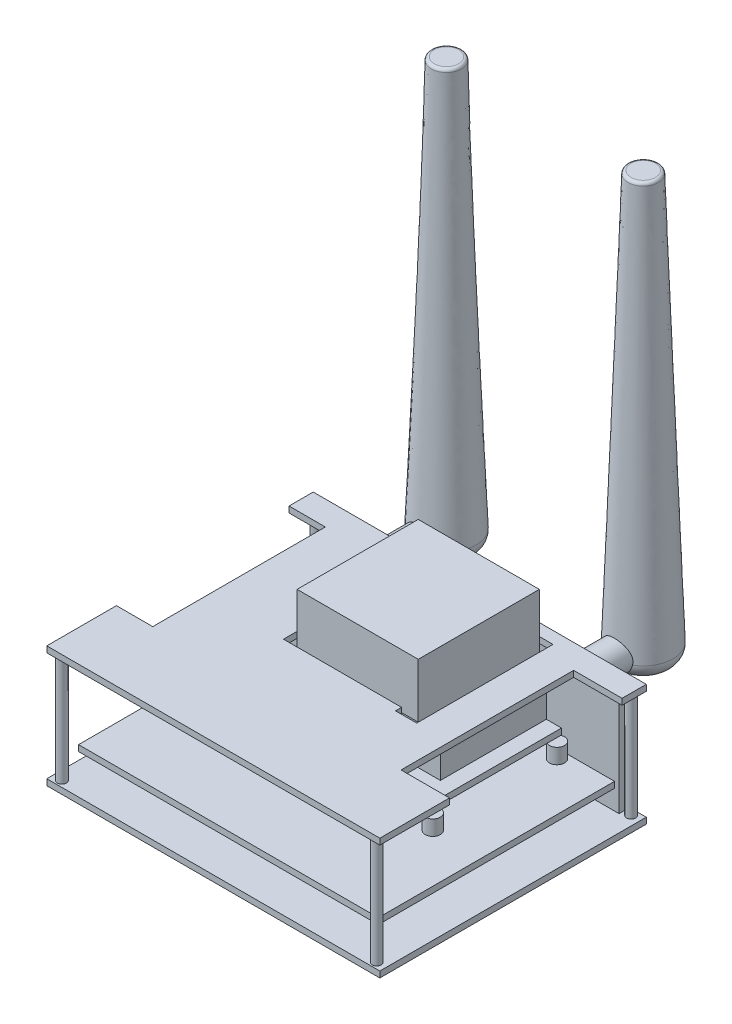
SolidWorks part; units mm, degrees
ref_plane "Front" through (0, 0, 0) normal (0, 0, 1) x (1, 0, 0)
ref_plane "Top" through (0, 0, 0) normal (0, 1, 0) x (1, 0, 0)
ref_plane "Right" through (0, 0, 0) normal (1, 0, 0) x (0, 0, -1)
sketch "草图1" plane through (0, 0, 0) normal (0, 1, 0) x (1, 0, 0)
  line L1 (0, 0) -> (110, 0)
  line L2 (0, 0) -> (0, 88)
  line L3 (0, 88) -> (110, 88)
  line L4 (110, 0) -> (110, 88)
  dimension "D1" = 110
  dimension "D2" = 88
extrude "凸台-拉伸1" add sketch "草图1" along normal blind 2
sketch "草图2" plane through (0, 2, 0) normal (0, 1, 0) x (1, 0, 0)
  line L0 (0, 88) -> (0, 0) construction
  line L1 (0, 0) -> (110, 0) construction
  line L2 (110, 88) -> (0, 88) construction
  line L3 (110, 0) -> (110, 88) construction
  circle A0 centre (3, 2) radius 1.5
  circle A1 centre (107, 86) radius 1.5
  circle A2 centre (3, 86) radius 1.5
  circle A3 centre (107, 2) radius 1.5
  dimension "D1" = 3
  dimension "D2" = 2
  dimension "D3" = 3
  dimension "D4" = 2
  dimension "D5" = 2
  dimension "D6" = 3
  dimension "D7" = 3
  dimension "D8" = 2
extrude "凸台-拉伸2" add sketch "草图2" along normal blind 36
sketch "草图3" plane through (0, 38, 0) normal (0, 1, 0) x (1, 0, 0)
  line L0 (110, 23) -> (110, 0)
  line L1 (0, 88) -> (110, 88)
  line L2 (0, 88) -> (0, 80)
  line L3 (0, 0) -> (110, 0)
  line L4 (110, 88) -> (110, 80)
  line L5 (110, 80) -> (94, 80)
  line L7 (110, 23) -> (94, 23)
  line L8 (94, 80) -> (94, 23)
  line L9 (0, 80) -> (12, 80)
  line L11 (0, 23) -> (12, 23)
  line L12 (12, 80) -> (12, 23)
  line L13 (37.1847, 84) -> (83.1847, 84)
  line L14 (37.1847, 84) -> (37.1847, 41)
  line L15 (37.1847, 41) -> (76.1847, 41)
  line L16 (83.1847, 84) -> (83.1847, 41)
  line L17 (0, 23) -> (0, 0)
  line L20 (83.1847, 41) -> (83.1847, 39)
  line L21 (83.1847, 39) -> (76.1847, 39)
  line L22 (76.1847, 41) -> (76.1847, 39)
  dimension "D1" = 16
  dimension "D2" = 57
  dimension "D3" = 23
  dimension "D4" = 12
  dimension "D5" = 57
  dimension "D6" = 8
  dimension "D7" = 39
  dimension "D8" = 7
  dimension "D9" = 43
  dimension "D10" = 4
  dimension "D11" = 2
extrude "凸台-拉伸3" add sketch "草图3" along normal blind 2
sketch "草图4" plane through (0, 2, 0) normal (0, 1, 0) x (1, 0, 0)
  line L0 (110, 88) -> (0, 88) construction
  line L1 (5.5, 86.5) -> (104.5, 86.5)
  line L2 (5.5, 86.5) -> (5.5, 84.5)
  line L3 (5.5, 84.5) -> (104.5, 84.5)
  line L4 (104.5, 86.5) -> (104.5, 84.5)
  circle A0 centre (3, 86) radius 1.5 construction
  circle A1 centre (107, 86) radius 1.5 construction
  point P6 (5.5, 85.5)
  dimension "D4" = 2.5
  dimension "D1" = 1.5
  dimension "D2" = 2
  dimension "D3" = 2.5
extrude "凸台-拉伸4" add sketch "草图4" along normal blind 36
sketch "草图5" plane through (0, 0, -86.5) normal (0, 0, -1) x (-1, 0, 0)
  line L0 (-110, 40) -> (0, 40) construction
  line L1 (-104.5, 38) -> (-104.5, 2) construction
  line L2 (-5.5, 38) -> (-5.5, 2) construction
  circle A0 centre (-87.5, 31) radius 5
  circle A1 centre (-22.5, 31) radius 5
  dimension "D1" = 9
  dimension "D2" = 17
  dimension "D3" = 9
  dimension "D4" = 17
extrude "凸台-拉伸5" add sketch "草图5" along normal blind 18
ref_plane "基准面1" through (0, 25, 0) normal (0, 1, 0) x (1, 0, 0)
sketch "草图6" plane through (0, 25, 0) normal (0, 1, 0) x (1, 0, 0)
  line L0 (92.5, 104.5) -> (82.5, 104.5) construction
  circle A0 centre (87.5, 109.5) radius 10
  dimension "D1" = 5
sketch "草图7" plane through (0, 25, 0) normal (0, 1, 0) x (1, 0, 0)
  line L0 (27.5, 104.5) -> (17.5, 104.5) construction
  circle A0 centre (22.5, 109.5) radius 10
  dimension "D1" = 5
ref_plane "基准面2" through (0, 165, 0) normal (0, 1, 0) x (1, 0, 0)
sketch "草图9" plane through (0, 165, 0) normal (0, 1, 0) x (1, 0, 0)
  circle A0 centre (87.5, 109.5) radius 5
sketch "草图10" plane through (0, 165, 0) normal (0, 1, 0) x (1, 0, 0)
  circle A0 centre (22.5, 109.5) radius 5
loft "放样1" add profiles "草图6", "草图9" connector at (97.4281, 25, -108.3028) connector at (92.4633, 165, -110.1048)
loft "放样2" add profiles "草图7", "草图10" connector at (12.7367, 25, -107.337) connector at (19.296, 165, -105.6615)
fillet "圆角1" radius 5 2 edges at (22.5, 25, -99.5) (87.5, 25, -99.5)
fillet "圆角2" radius 1 2 edges at (87.5, 165, -104.5) (22.5, 165, -104.5)
sketch "草图11" plane through (0, 2, 0) normal (0, 1, 0) x (1, 0, 0)
  line L0 (0, 88) -> (0, 0) construction
  line L1 (0, 0) -> (110, 0) construction
  line L2 (110, 88) -> (0, 88) construction
  line L3 (110, 0) -> (110, 88) construction
  circle A0 centre (10, 20) radius 1.5
  circle A1 centre (95, 22) radius 1.5
  circle A2 centre (10, 80) radius 1.5
  circle A3 centre (95, 80) radius 1.5
  dimension "D1" = 10
  dimension "D2" = 20
  dimension "D3" = 10
  dimension "D4" = 8
  dimension "D5" = 15
  dimension "D6" = 22
  dimension "D7" = 15
  dimension "D8" = 8
extrude "凸台-拉伸6" add sketch "草图11" along normal blind 8
sketch "草图12" plane through (0, 10, 0) normal (0, 1, 0) x (1, 0, 0)
  line L1 (5.5, 83) -> (104.5, 83)
  line L2 (5.5, 83) -> (5.5, 5)
  line L3 (5.5, 5) -> (104.5, 5)
  line L4 (104.5, 83) -> (104.5, 5)
  line L5 (0, 88) -> (0, 0) construction
  line L7 (104.5, 86.5) -> (5.5, 86.5) construction
  point P4 (5.5, 44)
  point P9 (0, 44)
  point P10 (55, 83)
  point P13 (55, 86.5)
  dimension "D1" = 99
  dimension "D2" = 78
  dimension "D3" = 0
  dimension "D4" = 0
extrude "凸台-拉伸7" add sketch "草图12" along normal blind 2
sketch "草图13" plane through (0, 12, 0) normal (0, 1, 0) x (1, 0, 0)
  line L0 (5.5, 83) -> (5.5, 5) construction
  line L1 (104.5, 83) -> (5.5, 83) construction
  line L2 (104.5, 5) -> (104.5, 83) construction
  circle A0 centre (21.5, 80) radius 2.5
  circle A1 centre (21.5, 39) radius 2.5
  circle A2 centre (88.5, 39) radius 2.5
  circle A3 centre (88.5, 80) radius 2.5
  dimension "D1" = 16
  dimension "D2" = 3
  dimension "D3" = 3
  dimension "D4" = 16
  dimension "D5" = 41
  dimension "D6" = 0
  dimension "D7" = 0
  dimension "D8" = 0
extrude "凸台-拉伸8" add sketch "草图13" along normal blind 5
sketch "草图14" plane through (0, 17, 0) normal (0, 1, 0) x (1, 0, 0)
  line L0 (110, 88) -> (0, 88) construction
  line L1 (22.5, 82.5) -> (87.5, 82.5)
  line L2 (22.5, 82.5) -> (22.5, 36.5)
  line L3 (22.5, 36.5) -> (87.5, 36.5)
  line L4 (87.5, 82.5) -> (87.5, 36.5)
  circle A0 centre (21.5, 39) radius 2.5 construction
  point P4 (55, 82.5)
  point P7 (55, 88)
  point P8 (22.5, 59.5)
  dimension "D1" = 65
  dimension "D2" = 46
  dimension "D3" = 0
  dimension "D4" = 20.5
extrude "凸台-拉伸9" add sketch "草图14" along normal blind 2
sketch "草图15" plane through (0, 19, 0) normal (0, 1, 0) x (1, 0, 0)
  line L0 (110, 88) -> (0, 88) construction
  line L1 (27.5, 82.5) -> (82.5, 82.5)
  line L2 (27.5, 82.5) -> (27.5, 47.5)
  line L3 (27.5, 47.5) -> (82.5, 47.5)
  line L4 (82.5, 82.5) -> (82.5, 47.5)
  line L5 (87.5, 82.5) -> (22.5, 82.5) construction
  point P4 (55, 82.5)
  point P7 (55, 88)
  dimension "D1" = 55
  dimension "D2" = 35
  dimension "D3" = 0
  dimension "D4" = 0
extrude "凸台-拉伸10" add sketch "草图15" along normal blind 18
sketch "草图16" plane through (0, 37, 0) normal (0, 1, 0) x (1, 0, 0)
  line L0 (83.1847, 84) -> (37.1847, 84) construction
  line L1 (40.1847, 82.5) -> (80.1847, 82.5)
  line L2 (40.1847, 82.5) -> (40.1847, 42.5)
  line L3 (40.1847, 42.5) -> (80.1847, 42.5)
  line L4 (80.1847, 82.5) -> (80.1847, 42.5)
  line L5 (37.1847, 84) -> (37.1847, 41) construction
  point P4 (60.1847, 82.5)
  point P7 (60.1847, 84)
  point P8 (40.1847, 62.5)
  point P11 (37.1847, 62.5)
  dimension "D1" = 40
  dimension "D2" = 40
  dimension "D3" = 0
  dimension "D4" = 0
extrude "凸台-拉伸11" add sketch "草图16" along normal blind 18
